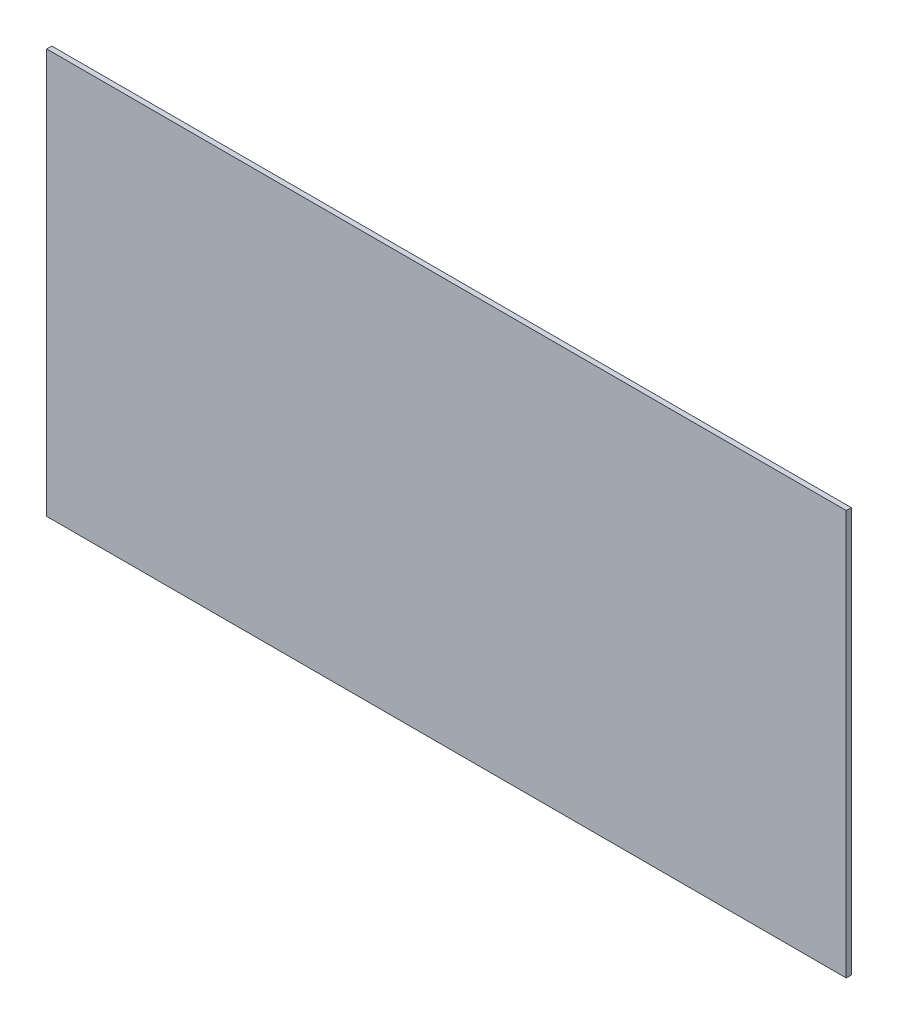
SolidWorks part; units mm, degrees
material "Polypropylene"
ref_plane "Front Plane" through (0, 0, 0) normal (0, 0, 1) x (1, 0, 0)
ref_plane "Top Plane" through (0, 0, 0) normal (0, 1, 0) x (1, 0, 0)
ref_plane "Right Plane" through (0, 0, 0) normal (1, 0, 0) x (0, 0, -1)
sketch "Sketch1" plane through (0, 0, 0) normal (0, 0, 1) x (1, 0, 0)
  line L1 (0, 0) -> (752.475, 0)
  line L2 (0, 0) -> (0, -381)
  line L3 (0, -381) -> (752.475, -381)
  line L4 (752.475, 0) -> (752.475, -381)
  dimension "D1" = 381
  dimension "D2" = 752.475
extrude "Boss-Extrude1" add sketch "Sketch1" along normal blind 4.7625
